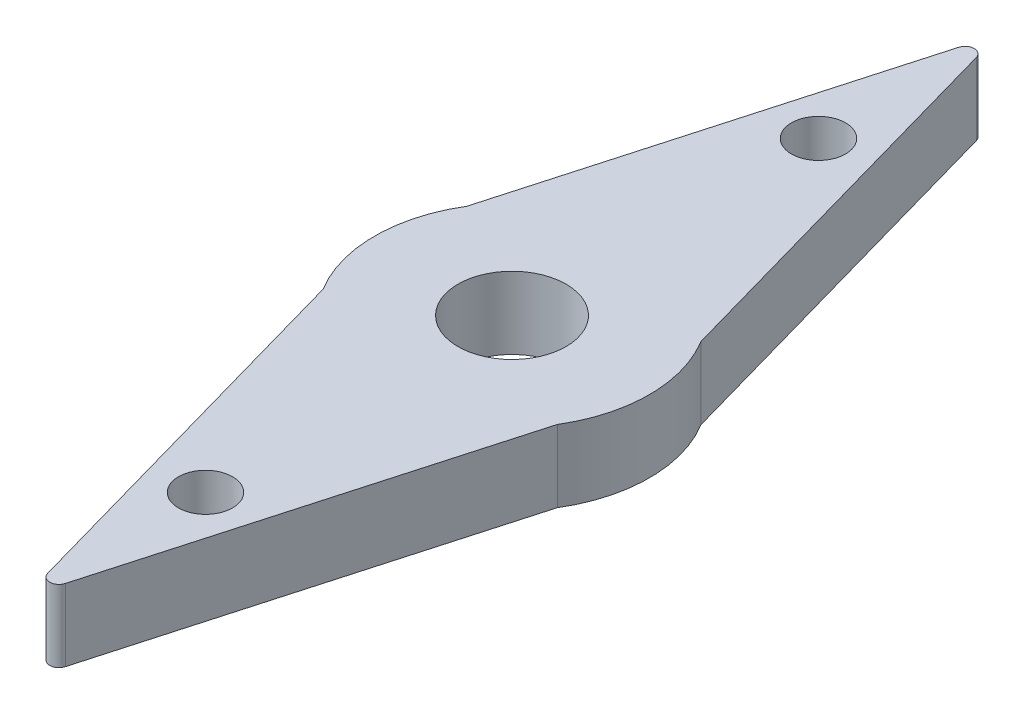
SolidWorks part; units mm, degrees
ref_plane "Front Plane" through (0, 0, 0) normal (0, 0, 1) x (1, 0, 0)
ref_plane "Top Plane" through (0, 0, 0) normal (0, 1, 0) x (1, 0, 0)
ref_plane "Right Plane" through (0, 0, 0) normal (1, 0, 0) x (0, 0, -1)
sketch "Sketch1" plane through (0, 0, 0) normal (0, 1, 0) x (1, 0, 0)
  circle A0 centre (0, 0) radius 3.81
  dimension "D1" = 7.62
extrude "Boss-Extrude1" add sketch "Sketch1" along normal blind 2
sketch "Sketch2" plane through (0, 2, 0) normal (0, 1, 0) x (1, 0, 0)
  line L0 (-3.81, 0) -> (3.81, 0) construction
  line L1 (3.81, 0) -> (0, 13.5)
  line L2 (0, 13.5) -> (-3.81, 0)
  line L3 (0, -13.5) -> (-3.81, 0)
  line L4 (3.81, 0) -> (0, -13.5)
  line L5 (-3.81, 0) -> (3.81, 0)
  circle A0 centre (0, 0) radius 3.81 construction
  circle M2 centre (0, 0) radius 3.81
  dimension "D1" = 27
extrude "Boss-Extrude2" add sketch "Sketch2" against normal up to surface (2 mm away) contours L4 L3 M2 | L1 L2 M2 region at (0, 2, -6.7168) region at (0, 2, 6.7168) up to face at (0, 0, 3.81)
fillet "Fillet1" radius 0.254 2 edges at (0, 1, 13.5) (0, 1, -13.5)
sketch "Sketch3" plane through (0, 2, 0) normal (0, 1, 0) x (1, 0, 0)
  line L0 (0, 12.8188) -> (0, -12.8188) construction
  line L1 (-3.81, 0) -> (3.81, 0) construction
  arc A0 (0.2445, 12.6338) -> (-0.2445, 12.6338) centre (0, 12.5648) ccw construction
  arc A1 (-0.2445, -12.6338) -> (0.2445, -12.6338) centre (0, -12.5648) ccw construction
  arc A2 (-3.2478, 1.9919) -> (-3.2478, -1.9919) centre (0, 0) ccw construction
  arc A3 (3.2478, -1.9919) -> (3.2478, 1.9919) centre (0, 0) ccw construction
  circle A4 centre (0, 8.5) radius 0.75
  circle A5 centre (0, -8.5) radius 0.75
  dimension "D1" = 8.5
  dimension "D2" = 1.5
extrude "Cut-Extrude1" cut sketch "Sketch3" against normal up to surface (2 mm away) up to face at (0, 0, 0)
sketch "Sketch4" plane through (0, 0, 0) normal (0, -1, 0) x (1, 0, 0)
  circle A0 centre (0, 0) radius 1.5
  dimension "D1" = 3
extrude "Cut-Extrude2" cut sketch "Sketch4" against normal through all
